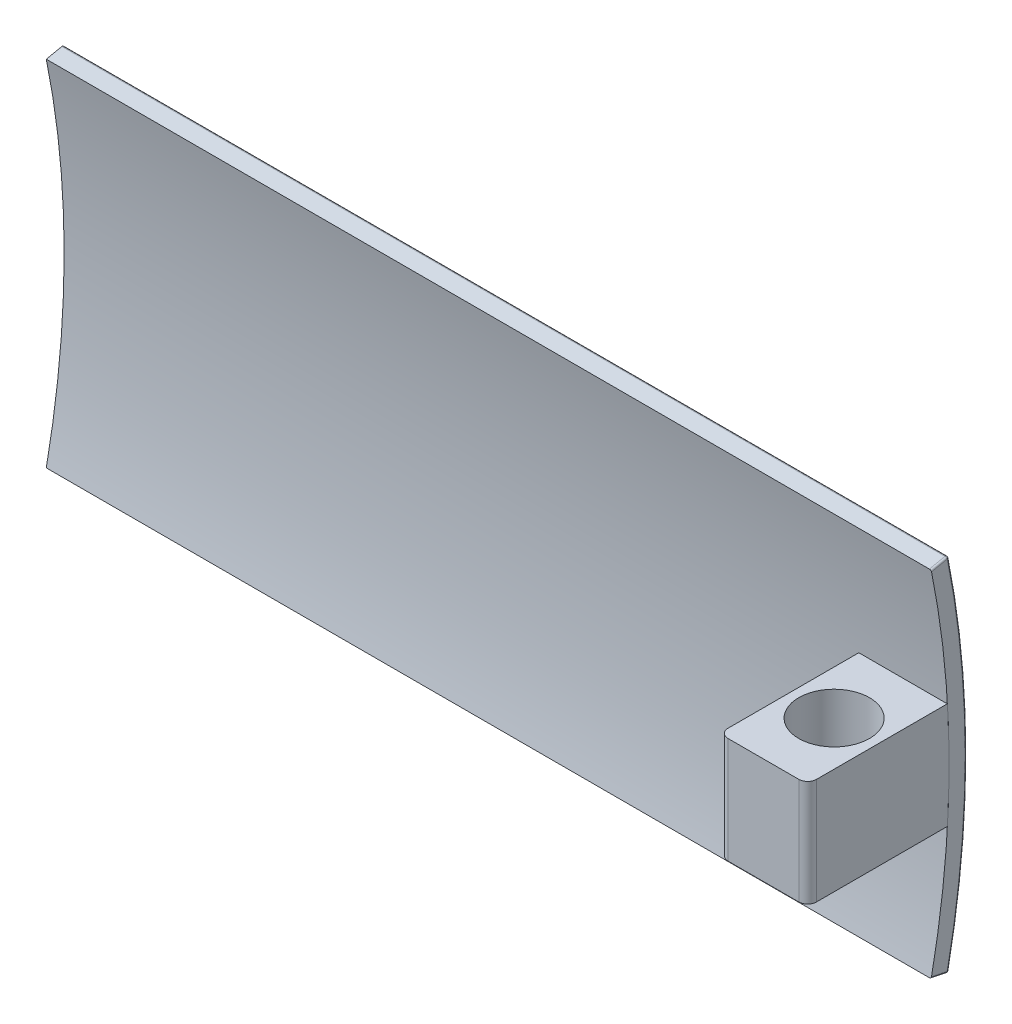
SolidWorks part; units mm, degrees
ref_plane "Front Plane" through (0, 0, 0) normal (0, 0, 1) x (1, 0, 0)
ref_plane "Top Plane" through (0, 0, 0) normal (0, 1, 0) x (1, 0, 0)
ref_plane "Right Plane" through (0, 0, 0) normal (1, 0, 0) x (0, 0, -1)
sketch "airflap" plane through (0, 0, 0) normal (1, 0, 0) x (0, 0, -1)
  line L0 (0, 0) -> (0, 50) construction
  line L1 (0, 0) -> (0, -50) construction
  line L2 (49.9696, 10.2) -> (48.9898, 10)
  line L3 (-48.9898, -10) -> (48.9898, -10) construction
  line L4 (-48.9898, -10) -> (-48.9898, 10) construction
  line L5 (-48.9898, 10) -> (48.9898, 10) construction
  line L6 (48.9898, -10) -> (48.9898, 10) construction
  line L7 (-48.9898, -10) -> (48.9898, 10) construction
  line L8 (-48.9898, 10) -> (48.9898, -10) construction
  line L9 (48.9898, -10) -> (49.9696, -10.2)
  arc A0 (48.9898, 10) -> (48.9898, -10) centre (0, 0) cw
  arc A1 (49.9696, 10.2) -> (49.9696, -10.2) centre (0, 0) cw
  dimension "D2" = 20
  dimension "D3" = 50
  dimension "D4" = 51
  dimension "D1" = 50
extrude "Boss-Extrude1" add sketch "airflap" along normal blind 50
fillet "Fillet3" radius 0.1 5 edges at (50, 10.1, -49.4797) (50, -10.1, -49.4797) (25, -10.2, -49.9696) (25, 10.2, -49.9696) (50, 0, -51)
ref_plane "hinge sketch" through (50, 0, 0) normal (1, 0, 0) x (0, 0, -1)
sketch "inner-hinge" plane through (50, 0, 0) normal (1, 0, 0) x (0, 0, -1)
  line L0 (49.0097, 9.902) -> (49.0097, -9.902) construction
  line L1 (49.0097, 0) -> (50, 0) construction
  line L2 (49.0097, 3) -> (42.0097, 3)
  line L4 (49.0097, -3) -> (42.0097, -3)
  line L5 (42.0097, 3) -> (42.0097, -3)
  line L6 (49.0097, 3) -> (49.9099, 3)
  line L8 (49.0097, -3) -> (49.9099, -3)
  line L9 (49.0097, 0) -> (42.0097, 0) construction
  arc A0 (49.0097, -9.902) -> (49.0097, 9.902) centre (0, 0) ccw construction
  arc A1 (49.9099, 3) -> (49.9099, -3) centre (0, 0) cw
  point P13 (0, 0)
  point P17 (0, 0)
  point P20 (0, 0)
  dimension "D1" = 6
  dimension "D2" = 42.0097
  dimension "D3" = 7
extrude "Boss-Extrude2" add sketch "inner-hinge" against normal blind 5 separate body
ref_plane "inner-screw hinge" through (0, 0, 0) normal (0, 1, 0) x (1, 0, 0)
sketch "cutout-hinge" plane through (0, 0, 0) normal (0, 1, 0) x (1, 0, 0)
  line L0 (47.5, 42.0097) -> (47.5, 50) construction
  line L1 (45, 42.0097) -> (50, 42.0097) construction
  line L2 (45, 42.0097) -> (50, 42.0097) construction
  circle A0 centre (47.5, 46.0048) radius 2
  point P6 (47.5, 51.0097)
  point P7 (0, 0)
  point P8 (47.5, 53.8299)
  point P10 (0, 0)
  dimension "D1" = 4
  dimension "D2" = 7.9903
  dimension "D3" = 3.9952
extrude "Cut-Extrude1" cut sketch "cutout-hinge" against normal through all both and the other way through all
fillet "Fillet4" radius 0.5 2 edges at (50, 0, -42.0097) (45, 0, -42.0097)
equation "\"D3@cutout-hinge\" = \"D2@cutout-hinge\" / 2"
